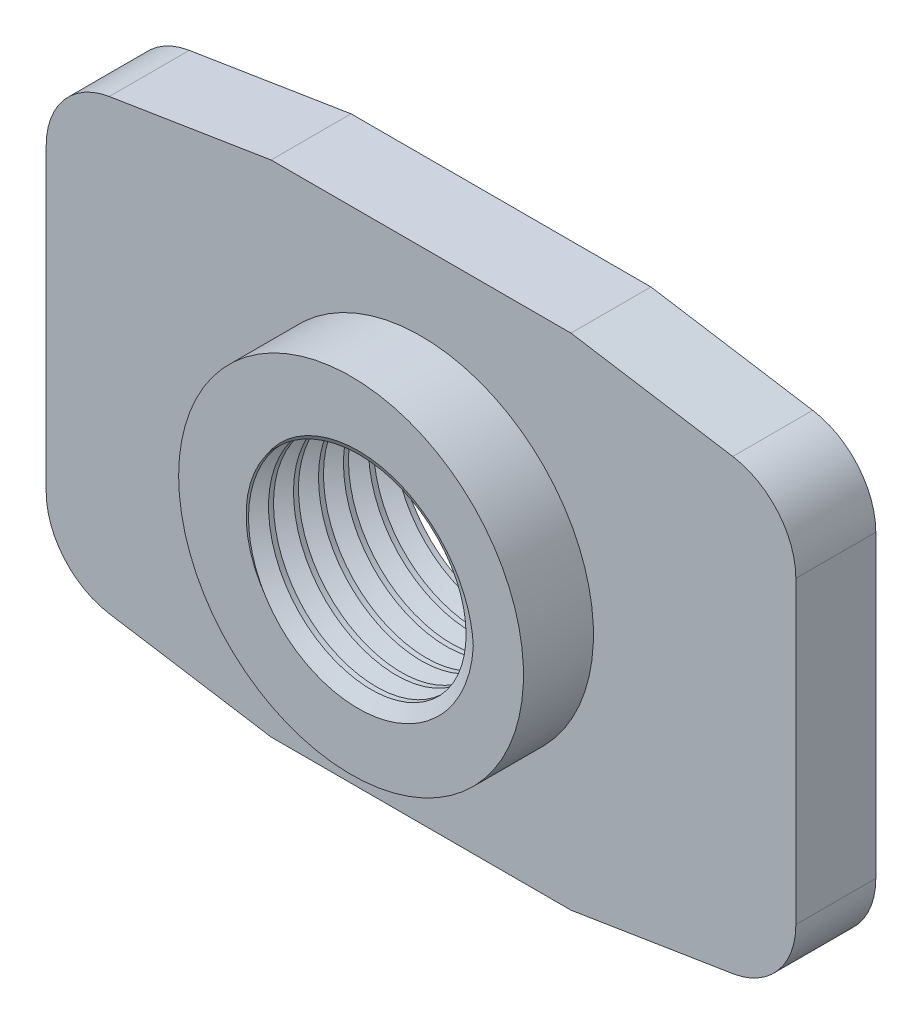
SolidWorks part; units mm, degrees
material "AISI 1020"
ref_plane "Front Plane" through (0, 0, 0) normal (0, 0, 1) x (1, 0, 0)
ref_plane "Top Plane" through (0, 0, 0) normal (0, 1, 0) x (1, 0, 0)
ref_plane "Right Plane" through (0, 0, 0) normal (1, 0, 0) x (0, 0, -1)
ref_plane "Plane1" through (0, 0, 1.6) normal (0, 0, 1) x (1, 0, 0)
sketch "Sketch1" plane through (0, 0, 1.6) normal (0, 0, 1) x (1, 0, 0)
  line L0 (3, -5) -> (6.0922, -4.5044)
  line L1 (6.0922, -4.5044) -> (7.5, 4.2787)
  line L2 (7.5, 4.2787) -> (3, 5)
  line L3 (3, 5) -> (-3, 5)
  line L4 (-3, 5) -> (-7.5, 4.2787)
  line L5 (-7.5, 4.2787) -> (-7.5, -4.2787)
  line L6 (-7.5, -4.2787) -> (-3, -5)
  line L7 (-3, -5) -> (3, -5)
extrude "Boss-Extrude1" add sketch "Sketch1" against normal blind 1.6
draft "Draft1" type of draft neutral plane draft angle 9.106 faces to draft 1 face at (6.7961, -0.1128, 0.8) neutral plane through (7.5, 4.2787, 0) neutral plane normal (0.1583, 0.9874, 0) parameters "D1"=9.106
ref_plane "Plane2" through (0, 0, 0) normal (0, -1, 0) x (1, 0, 0)
sketch "Sketch2" plane through (0, 0, 0) normal (0, -1, 0) x (1, 0, 0)
  line L0 (3.45, 3) -> (0, 3)
  line L1 (0, 3) -> (0, 1.6)
  line L2 (0, 1.6) -> (3.45, 1.6)
  line L3 (3.45, 1.6) -> (3.45, 3)
  line L4 (0, 3) -> (0, 1.6) construction
revolve "Revolve1" add sketch "Sketch2" angle 360 about L4 reverse direction yes
hole_wizard "Ø4.2 (4.2) Diameter Hole1" positions "Sketch4" profile "Sketch3" hole size "Ø4.2" standard "ANSI Metric"
sketch "Sketch4" plane through (0, 0, 3) normal (0, 0, 1) x (1, 0, 0)
  point P0 (0, 0)
sketch "Sketch3" plane through (0, 0, 3) normal (1, 0, 0) x (0, -1, 0)
  line L0 (0, 0) -> (0, 3)
  line L1 (0, 3) -> (2.1, 3)
  line L2 (2.1, 3) -> (2.1, 0)
  line L5 (2.1, 0) -> (0, 0)
  line L11 (0, -6.35) -> (0, 107.95) construction
  dimension "Thru Hole Dia." = 4.2
  dimension "Thru Hole Depth" = 3
fillet "Fillet1" radius 1.5 4 edges at (7.5, 4.2787, 0.8) (7.5, -4.2787, 0.8) (-7.5, 4.2787, 0.8) (-7.5, -4.2787, 0.8) tangent propagation no
sketch "Sketch6" plane through (0, 0, 0) normal (0, 1, 0) x (1, 0, 0)
  line L0 (3, 0) -> (-3, 0) construction
  line L1 (2.4464, 0) -> (1.9268, 0.3)
  line L2 (1.9268, 0.3) -> (1.9268, -0.3)
  line L3 (1.9268, -0.3) -> (2.4464, 0)
  circle A0 centre (2.1, 0) radius 0.1732 construction
  dimension "D1" = 2.1
  dimension "D2" = 0.6
sketch "Sketch7" plane through (0, 0, 3) normal (0, 0, 1) x (1, 0, 0)
  circle A0 centre (0, 0) radius 2.1 construction
  circle A1 centre (0, 0) radius 2.1
curve "Helix/Spiral1" pitch 0.5 height 3 radius 2.1 centre (0, 0, 3) axis (0, 0, -1) start towards (1, 0, 0)
sweep "Cut-Sweep1" cut profiles "Sketch6" path "Helix/Spiral1" align with end faces yes
